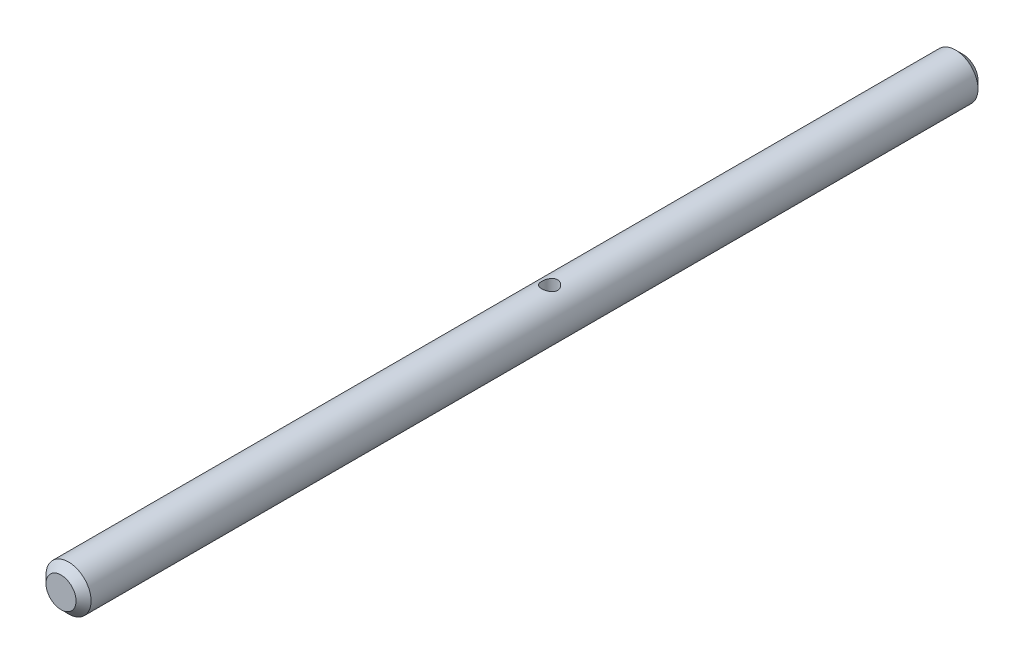
SolidWorks part; units mm, degrees
ref_plane "Płaszczyzna przednia" through (0, 0, 0) normal (0, 0, 1) x (1, 0, 0)
ref_plane "Płaszczyzna górna" through (0, 0, 0) normal (0, 1, 0) x (1, 0, 0)
ref_plane "Płaszczyzna prawa" through (0, 0, 0) normal (1, 0, 0) x (0, 0, -1)
sketch "Szkic1" plane through (0, 0, 0) normal (0, 0, 1) x (1, 0, 0)
  circle A0 centre (0, 0) radius 3
  dimension "D1" = 6
extrude "Dodanie-wyciągnięcie1" add sketch "Szkic1" along normal blind 65
extrude "Dodanie-wyciągnięcie2" add sketch "Szkic1<2>" against normal blind 120 from surface starting at face at (3, 0, 65)
sketch "Szkic1<2>" plane through (0, 0, 0) normal (0, 0, 1) x (1, 0, 0) same geometry as "Szkic1"
chamfer "Sfazowanie1" distance 1 angle 45 2 edges at (3, 0, 65) (3, 0, -55)
sketch "Szkic2" plane through (0, 0, 0) normal (0, 1, 0) x (1, 0, 0)
  circle A0 centre (0, 0) radius 1.05
  dimension "D1" = 2.1
extrude "Wytnij-wyciągnięcie1" cut sketch "Szkic2" against normal through all both and the other way through all
